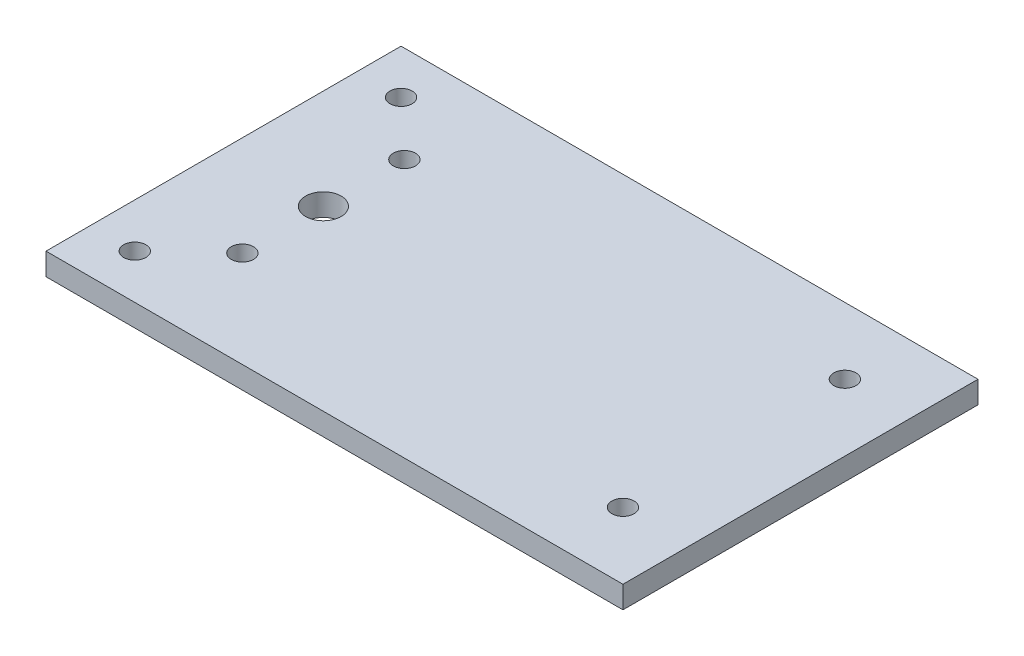
SolidWorks part; units mm, degrees
ref_plane "Front Plane" through (0, 0, 0) normal (0, 0, 1) x (1, 0, 0)
ref_plane "Top Plane" through (0, 0, 0) normal (0, 1, 0) x (1, 0, 0)
ref_plane "Right Plane" through (0, 0, 0) normal (1, 0, 0) x (0, 0, -1)
sketch "Sketch1" plane through (0, 0, 0) normal (0, 1, 0) x (1, 0, 0)
  line L0 (-69.7183, -5.3521) -> (60.2817, -5.3521) construction
  line L1 (-69.7183, 34.6479) -> (60.2817, 34.6479)
  line L2 (-69.7183, 34.6479) -> (-69.7183, -45.3521)
  line L3 (-69.7183, -45.3521) -> (60.2817, -45.3521)
  line L4 (60.2817, 34.6479) -> (60.2817, -45.3521)
  line L5 (-47.2183, -5.3521) -> (-47.2183, 47.2908) construction
  circle A0 centre (-47.2183, -5.3521) radius 4
  circle A1 centre (45.2817, 19.6479) radius 2.5
  circle A2 centre (-59.7183, 24.6479) radius 2.5
  circle A3 centre (45.2817, -30.3521) radius 2.5
  circle A4 centre (-59.7183, -35.3521) radius 2.5
  circle A5 centre (-47.2183, 12.8979) radius 2.5
  circle A6 centre (-47.2183, -23.6021) radius 2.5
  dimension "D3" = 8
  dimension "D4" = 5
  dimension "D5" = 5
  dimension "D6" = 15
  dimension "D7" = 15
  dimension "D8" = 10
  dimension "D9" = 10
  dimension "D10" = 22.5
  dimension "D11" = 5
  dimension "D12" = 18.25
  dimension "D1" = 130
  dimension "D2" = 80
extrude "Boss-Extrude1" add sketch "Sketch1" along normal blind 5
